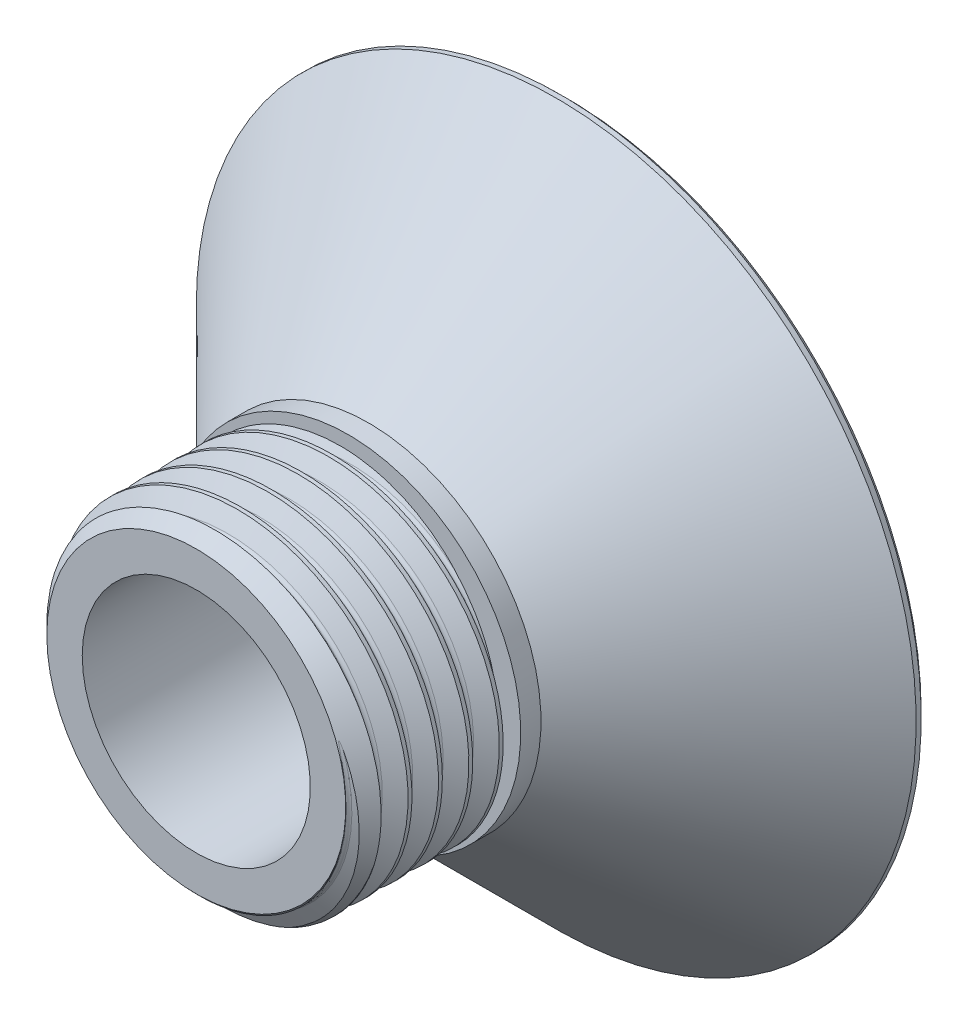
SolidWorks part; units mm, degrees
ref_plane "Front Plane" through (0, 0, 0) normal (0, 0, 1) x (1, 0, 0)
ref_plane "Top Plane" through (0, 0, 0) normal (0, 1, 0) x (1, 0, 0)
ref_plane "Right Plane" through (0, 0, 0) normal (1, 0, 0) x (0, 0, -1)
sketch "Sketch1" plane through (0, 0, 0) normal (1, 0, 0) x (0, 0, -1)
  line L1 (0, 0) -> (-153.1218, 0) construction
  line L2 (0, 6.5) -> (0, 35.5)
  line L3 (0, 35.5) -> (-1, 35.5)
  line L4 (-1, 35.5) -> (-19.5, 17)
  line L5 (-19.5, 17) -> (-21.5, 17)
  line L6 (-21.5, 17) -> (-21.5, 14.75)
  line L7 (-21.5, 14.75) -> (-36.5, 14.75)
  line L8 (-36.5, 14.75) -> (-36.5, 11.25)
  line L9 (-36.5, 11.25) -> (-2, 11.25)
  line L10 (-2, 11.25) -> (-2, 6.5)
  line L11 (-2, 6.5) -> (0, 6.5)
  dimension "D1" = 45
  dimension "D3" = 34
  dimension "D4" = 1
  dimension "D5" = 29.5
  dimension "D6" = 2
  dimension "D7" = 15
  dimension "D8" = 22.5
  dimension "D9" = 13
  dimension "D10" = 2
  dimension "D11" = 21.5
revolve "Revolve1" add sketch "Sketch1" angle 360 about L1
sketch "Sketch2" plane through (0, 0, 21.5) normal (0, 0, 1) x (1, 0, 0)
  circle A0 centre (0, 0) radius 14.75 construction
  circle A1 centre (0, 0) radius 14.75
curve "Helix/Spiral1" pitch 3 height 18 radius 14.75 centre (0, 0, 21.5) axis (0, 0, 1) start towards (1, 0, 0)
sketch "Sketch4" plane through (0, 0, 0) normal (0, 1, 0) x (1, 0, 0)
  line L0 (14.9658, -36.1259) -> (16.5798, -35.194)
  line L1 (16.5798, -35.194) -> (16.5798, -34.816)
  line L2 (14.7498, -36.5) -> (14.7498, -33.51)
  line L3 (-14.75, -36.5) -> (14.75, -36.5) construction
  line L4 (16.5798, -35.005) -> (14.7498, -35.005) construction
  line L5 (14.9658, -33.8841) -> (16.5798, -34.816)
  arc A0 (14.9658, -36.1259) -> (14.7498, -36.5) centre (15.1818, -36.5) ccw
  arc A1 (14.9658, -33.8841) -> (14.7498, -33.51) centre (15.1818, -33.51) cw
  spline S0 degree 3 poles (14.75, -21.5) (14.75, -21.5591) (14.057, -21.6784) (11.0817, -21.8564) (6.5803, -22.0347) (1.1728, -22.2129) (-4.3963, -22.3911) (-9.36, -22.5693) (-13.0346, -22.7475) (-14.9143, -22.9257) (-14.7401, -23.104) (-12.5359, -23.2822) (-8.6055, -23.4604) (-3.49, -23.6386) (2.1062, -23.8168) (7.4123, -23.995) (11.6976, -24.1733) (14.3721, -24.3515) (15.0673, -24.5297) (13.6876, -24.7079) (10.4229, -24.8861) (5.7229, -25.0644) (0.2348, -25.2426) (-5.2857, -25.4208) (-10.0782, -25.599) (-13.4829, -25.7772) (-15.0308, -25.9554) (-14.5088, -26.1337) (-11.9888, -26.3119) (-7.8177, -26.4901) (-2.5701, -26.6683) (3.0315, -26.8465) (8.2156, -27.0248) (12.2683, -27.203) (14.6315, -27.3812) (14.9798, -27.5594) (13.2652, -27.7376) (9.7238, -27.9158) (4.8433, -28.0941) (-0.7041, -28.2723) (-6.1546, -28.4505) (-10.7575, -28.6287) (-13.879, -28.8069) (-15.0892, -28.9851) (-14.2214, -29.1634) (-11.3952, -29.3416) (-6.9997, -29.5198) (-1.6403, -29.698) (3.945, -29.8762) (8.9871, -30.0545) (12.7915, -30.2327) (14.8343, -30.4109) (14.8343, -30.5891) (12.7915, -30.7673) (8.9871, -30.9455) (3.945, -31.1238) (-1.6403, -31.302) (-6.9997, -31.4802) (-11.3952, -31.6584) (-14.2214, -31.8366) (-15.0892, -32.0149) (-13.879, -32.1931) (-10.7575, -32.3713) (-6.1546, -32.5495) (-0.7041, -32.7277) (4.8433, -32.9059) (9.7238, -33.0842) (13.2652, -33.2624) (14.9798, -33.4406) (14.6315, -33.6188) (12.2683, -33.797) (8.2156, -33.9752) (3.0315, -34.1535) (-2.5701, -34.3317) (-7.8177, -34.5099) (-11.9888, -34.6881) (-14.5088, -34.8663) (-15.0308, -35.0446) (-13.4829, -35.2228) (-10.0782, -35.401) (-5.2857, -35.5792) (0.2348, -35.7574) (5.7229, -35.9356) (10.4229, -36.1139) (13.6876, -36.2921) (15.0673, -36.4703) (14.3721, -36.6485) (11.6976, -36.8267) (7.4123, -37.005) (2.1062, -37.1832) (-3.49, -37.3614) (-8.6055, -37.5396) (-12.5359, -37.7178) (-14.7401, -37.896) (-14.9143, -38.0743) (-13.0346, -38.2525) (-9.36, -38.4307) (-4.3963, -38.6089) (1.1728, -38.7871) (6.5803, -38.9653) (11.0817, -39.1436) (14.057, -39.3216) (14.75, -39.4409) (14.75, -39.5) knots 0 0 0 0 0.009901 0.019802 0.029703 0.039604 0.049505 0.059406 0.069307 0.079208 0.089109 0.09901 0.108911 0.118812 0.128713 0.138614 0.148515 0.158416 0.168317 0.178218 0.188119 0.19802 0.207921 0.217822 0.227723 0.237624 0.247525 0.257426 0.267327 0.277228 0.287129 0.29703 0.306931 0.316832 0.326733 0.336634 0.346535 0.356436 0.366337 0.376238 0.386139 0.39604 0.405941 0.415842 0.425743 0.435644 0.445545 0.455446 0.465347 0.475248 0.485149 0.49505 0.50495 0.514851 0.524752 0.534653 0.544554 0.554455 0.564356 0.574257 0.584158 0.594059 0.60396 0.613861 0.623762 0.633663 0.643564 0.653465 0.663366 0.673267 0.683168 0.693069 0.70297 0.712871 0.722772 0.732673 0.742574 0.752475 0.762376 0.772277 0.782178 0.792079 0.80198 0.811881 0.821782 0.831683 0.841584 0.851485 0.861386 0.871287 0.881188 0.891089 0.90099 0.910891 0.920792 0.930693 0.940594 0.950495 0.960396 0.970297 0.980198 0.990099 1 1 1 1 construction
  dimension "D2" = 0.432
  dimension "D1" = 1.83
  dimension "D3" = 60
  dimension "D4" = 2.99
sweep "Sweep5" add profiles "Sketch4" path "Helix/Spiral1"
sketch "Sketch11" plane through (0, 0, 0) normal (0, 1, 0) x (1, 0, 0)
  line L0 (0, 0) -> (0, -46.1811) construction
  line L1 (17.2033, -36.5) -> (-17.0232, -36.5)
  line L2 (-17, -21.5) -> (17, -21.5) construction
  dimension "D1" = 15
extrude "Cut-Extrude1" cut sketch "Sketch11" against normal through all and the other way through all
sketch "Sketch12" plane through (0, 0, 0) normal (0, 1, 0) x (1, 0, 0)
  line L0 (0, 0) -> (0, -42.7931) construction
  line L1 (14.743, -36.5) -> (17.243, -34)
  line L2 (17.243, -34) -> (17.243, -36.5)
  line L3 (17.243, -36.5) -> (14.743, -36.5)
  dimension "D1" = 45
  dimension "D2" = 2.5
revolve "Cut-Revolve1" cut sketch "Sketch12" angle 360 about L0
chamfer "Chamfer1" distance 0.5 angle 45 2 edges at (-6.5, 0, 0) (-35.5, 0, 0)
